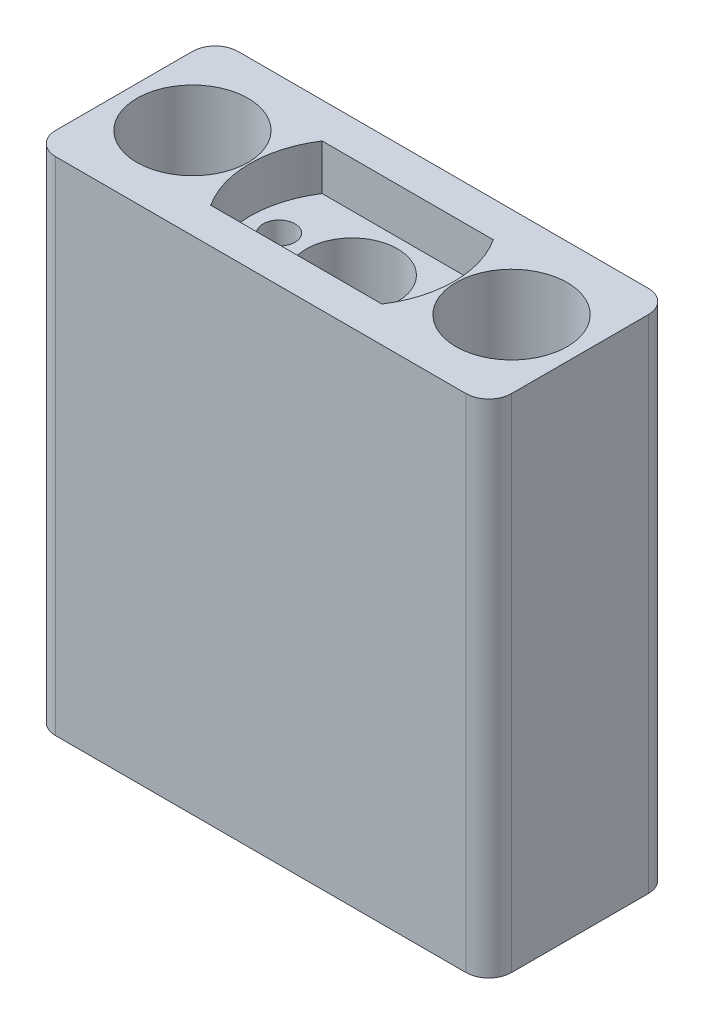
SolidWorks part; units mm, degrees
ref_plane "前视基准面" through (0, 0, 0) normal (0, 0, 1) x (1, 0, 0)
ref_plane "上视基准面" through (0, 0, 0) normal (0, 1, 0) x (1, 0, 0)
ref_plane "右视基准面" through (0, 0, 0) normal (1, 0, 0) x (0, 0, -1)
sketch "草图1" plane through (0, 0, 0) normal (0, 1, 0) x (1, 0, 0)
  line L1 (-25, -10) -> (25, -10)
  line L2 (-25, -10) -> (-25, 10)
  line L3 (-25, 10) -> (25, 10)
  line L4 (25, -10) -> (25, 10)
  line L5 (0, 10) -> (0, -10) construction
  line L6 (-25, 0) -> (25, 0) construction
  point P0 (0, 0)
extrude "凸台-拉伸1" add sketch "草图1" along normal blind 55
sketch "草图2" plane through (0, 55, 0) normal (0, 1, 0) x (1, 0, 0)
  line L1 (-9.3872, 6.1091) -> (9.3872, 6.1091)
  line L3 (-9.3872, -6.1091) -> (9.3872, -6.1091)
  arc A0 (-9.3872, 6.1091) -> (-9.3872, -6.1091) centre (0, 0) ccw
  arc A1 (9.3872, -6.1091) -> (9.3872, 6.1091) centre (0, 0) ccw
extrude "切除-拉伸1" cut sketch "草图2" against normal blind 5
sketch "草图3" plane through (0, 50, 0) normal (0, 1, 0) x (1, 0, 0)
  circle A0 centre (0, 0) radius 5
extrude "切除-拉伸2" cut sketch "草图3" against normal through all
sketch "草图4" plane through (0, 55, 0) normal (0, 1, 0) x (1, 0, 0)
  line L0 (11.2, 0) -> (17.5, 0)
  line L1 (0, 0) -> (0, 4.2582)
  arc A0 (9.3872, -6.1091) -> (9.3872, 6.1091) centre (0, 0) ccw construction
  circle A1 centre (17.5, 0) radius 6.1
  circle A2 centre (-17.5, 0) radius 6.1
extrude "切除-拉伸3" cut sketch "草图4" against normal blind 20 contours A2 | A1 region at (17.5, 55, 5.9275) region at (-17.5, 55, 0)
sketch "草图5" plane through (0, 35, 0) normal (0, 1, 0) x (1, 0, 0)
  circle A0 centre (-17.5, 0) radius 4
  circle A1 centre (17.5, 0) radius 4
extrude "切除-拉伸4" cut sketch "草图5" against normal through all
sketch "草图6" plane through (0, 50, 0) normal (0, 1, 0) x (1, 0, 0)
  circle A0 centre (8, 0) radius 1.75
  circle A1 centre (-8, 0) radius 1.75
extrude "切除-拉伸5" cut sketch "草图6" against normal blind 7
sketch "草图7" plane through (0, 0, 0) normal (0, -1, 0) x (1, 0, 0)
  circle A0 centre (-17.5, 0) radius 6.1 construction
  circle A1 centre (17.5, 0) radius 6.1 construction
  circle A2 centre (-17.5, 0) radius 6.1
  circle A3 centre (17.5, 0) radius 6.1
extrude "切除-拉伸6" cut sketch "草图7" against normal blind 20
fillet "圆角1" radius 2.5 4 edges at (25, 27.5, 10) (25, 27.5, -10) (-25, 27.5, 10) (-25, 27.5, -10)
